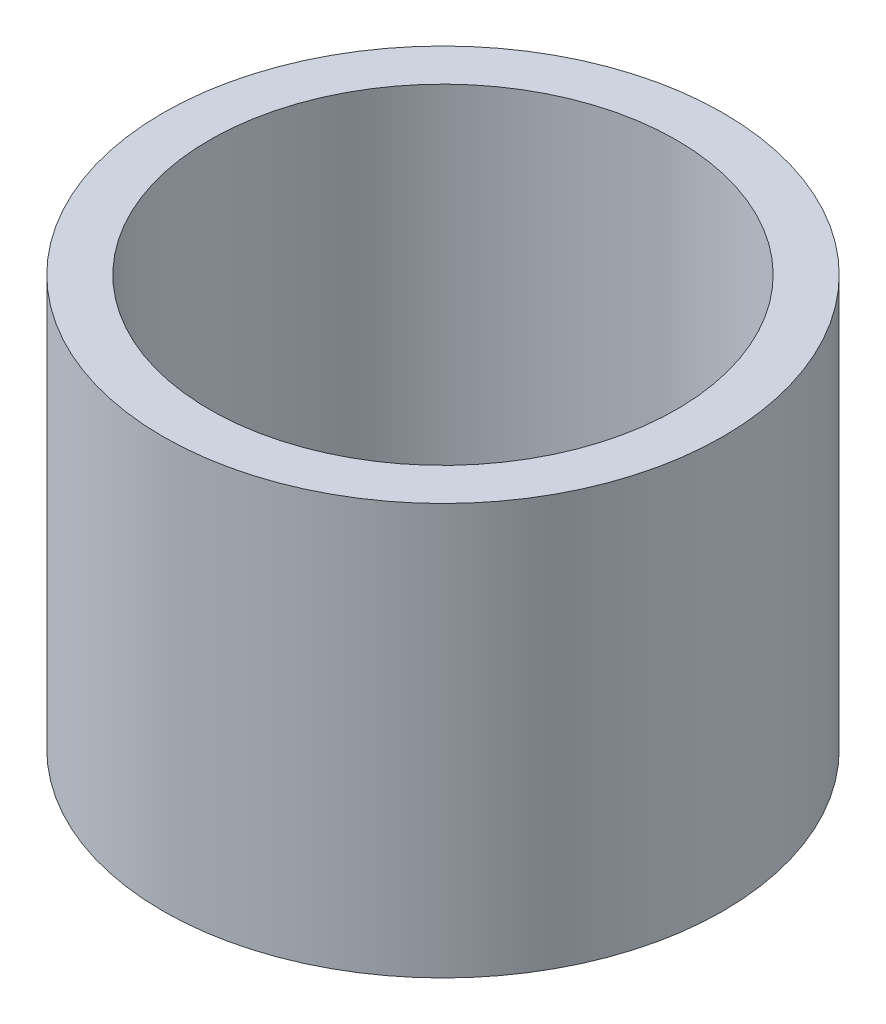
SolidWorks part; units mm, degrees
ref_plane "Front Plane" through (0, 0, 0) normal (0, 0, 1) x (1, 0, 0)
ref_plane "Top Plane" through (0, 0, 0) normal (0, 1, 0) x (1, 0, 0)
ref_plane "Right Plane" through (0, 0, 0) normal (1, 0, 0) x (0, 0, -1)
sketch "Sketch1" plane through (0, 0, 0) normal (0, 1, 0) x (1, 0, 0)
  line L0 (0, 0) -> (0, 11) construction
  line L1 (0, 0) -> (1.1498, 10.9397) construction
  line L2 (0, 0) -> (1.6069, 10.882) construction
  circle A0 centre (0, 0) radius 11 construction
  circle A1 centre (0, 0) radius 9.996 construction
  circle A2 centre (0, 0) radius 10.746 construction
  arc A3 (1.0449, 9.9412) -> (0.5705, 10.3364) centre (1.1029, 10.4932) cw
  arc A4 (2.5291, 10.9132) -> (0.5705, 10.5933) centre (1.5698, 10.6307) cw
  circle A5 centre (0, 0) radius 10.596 construction
  arc A6 (-0.4266, 10.7375) -> (0.4266, 10.7375) centre (0, 0) cw
  arc A7 (0.4266, 10.7375) -> (0.5705, 10.5933) centre (0.4206, 10.5876) cw
  arc A8 (2.5291, 10.9132) -> (0.5705, 10.3364) centre (1.5498, 10.6248) ccw
  arc A9 (-1.0449, 9.9412) -> (-0.5705, 10.3364) centre (-1.1029, 10.4932) ccw
  arc A10 (-2.5291, 10.9132) -> (-0.5705, 10.3364) centre (-1.5498, 10.6248) cw
  arc A11 (-2.5291, 10.9132) -> (-0.5705, 10.5933) centre (-1.5698, 10.6307) ccw
  arc A12 (-0.4266, 10.7375) -> (-0.5705, 10.5933) centre (-0.4206, 10.5876) ccw
  arc A13 (-1.0449, 9.9412) -> (1.0449, 9.9412) centre (0, 0) cw
  point P13 (1.5698, 10.6307)
  point P16 (0, 10.746)
  dimension "D1" = 22
  dimension "D6" = 0.555
  dimension "D7" = 1
  dimension "D9" = 0.15
  dimension "D2" = 6
  dimension "D3" = 2.4
  dimension "D4" = 1.004
  dimension "D5" = 0.75
  dimension "D8" = 0.15
extrude "Boss-Extrude1" add sketch "Sketch1" along normal blind 7 contours A9 A13 A3 A8 A4 A7 A6 A12 A11 A10
sketch "Sketch2" plane through (0, 0, 0) normal (0, -1, 0) x (1, 0, 0)
  circle A0 centre (0, 0) radius 9.996
  arc A2 (-0.8265, -9.9618) -> (0.8265, -9.9618) centre (0, 0) ccw construction
  arc A5 (-0.8265, -9.9618) -> (0.8265, -9.9618) centre (0, 0) ccw
  arc M3 (-0.739, -10.0741) -> (-0.5705, -10.3364) centre (-1.1029, -10.4932) cw
  arc M4 (-0.5705, -10.3364) -> (-0.5309, -10.6893) centre (-1.5498, -10.6248) cw
  arc M5 (-0.8265, -9.9618) -> (-0.739, -10.0741) centre (-1.5698, -10.6307) cw
  arc M6 (-0.5309, -10.6893) -> (-0.4266, -10.7375) centre (-0.4206, -10.5876) ccw
  arc M7 (-0.4266, -10.7375) -> (0.4266, -10.7375) centre (0, 0) ccw
  arc M8 (0.4266, -10.7375) -> (0.5309, -10.6893) centre (0.4206, -10.5876) ccw
  arc M9 (0.739, -10.0741) -> (0.8265, -9.9618) centre (1.5698, -10.6307) cw
  arc M10 (0.5309, -10.6893) -> (0.5705, -10.3364) centre (1.5498, -10.6248) cw
  arc M11 (0.5705, -10.3364) -> (0.739, -10.0741) centre (1.1029, -10.4932) cw
  arc M12 (0.8265, -9.9618) -> (-0.8265, -9.9618) centre (0, 0) cw
extrude "Boss-Extrude2" add sketch "Sketch2" against normal blind 7 contours A0 M3 M12 M11 M10 M9 M8 M7 M6 M5 M4
pattern_circular "CirPattern3" count 30 over 360 about axis through (0, 0, 0) along (0, 1, 0) of "Boss-Extrude1"
sketch "Sketch3" plane through (0, 7, 0) normal (0, 1, 0) x (1, 0, 0)
  circle A0 centre (0, 0) radius 11.946
  arc A3 (0.4742, 11.9366) -> (-0.4742, 11.9366) centre (0, 0) ccw
  arc A4 (0.4742, 11.9366) -> (-0.4742, 11.9366) centre (0, 0) ccw
  dimension "D1" = 1.2
extrude "Boss-Extrude3" add sketch "Sketch3" along normal blind 1.2 contours A0
sketch "Sketch4" plane through (0, 0, 0) normal (0, -1, 0) x (1, 0, 0)
  circle A0 centre (0, 0) radius 11.946 construction
  circle A1 centre (0, 0) radius 11.946
extrude "Boss-Extrude4" add sketch "Sketch4" along normal blind 1.2
sketch "Sketch12" plane through (0, 8.2, 0) normal (0, 1, 0) x (1, 0, 0)
  circle A0 centre (0, 0) radius 7.5
  dimension "D1" = 15
extrude "Boss-Extrude10" add sketch "Sketch12" along normal offset from surface (8.6 mm away) 18 up to face at (0, -1.2, -11.946)
sketch "Sketch5" plane through (0, 8.2, 0) normal (0, 1, 0) x (1, 0, 0)
  circle A0 centre (0, 0) radius 4
  dimension "D1" = 8
extrude "Cut-Extrude1" cut sketch "Sketch5" against normal through all both and the other way through all
chamfer "Chamfer1" distance 0.3 angle 45 3 edges at (0, 7, 11.946) (0, 0, -11.946) (0, 16.8, -7.5)
sketch "Sketch6" plane through (0, 8.2, 0) normal (0, 1, 0) x (1, 0, 0)
  line L0 (0, 0) -> (0, 7.3211) construction
  line L1 (0, 0) -> (0.9969, 7.2529) construction
  line L2 (0, 0) -> (1.3915, 7.1877) construction
  circle A0 centre (0, 0) radius 7.3211 construction
  circle A1 centre (0, 0) radius 6.3171 construction
  circle A2 centre (0, 0) radius 7.0671 construction
  circle A3 centre (0, 0) radius 6.9171 construction
  arc A4 (0.8602, 6.2583) -> (0.6496, 6.3326) centre (0.9358, 6.8081) cw
  arc A5 (0.364, 6.7355) -> (0.3434, 6.9175) centre (1.3432, 6.9383) cw
  arc A6 (-0.1976, 7.0644) -> (0.1976, 7.0644) centre (0, 0) cw
  arc A7 (0.1976, 7.0644) -> (0.3434, 6.9175) centre (0.1935, 6.9144) cw
  arc A8 (0.364, 6.7355) -> (0.6496, 6.3326) centre (0.9672, 6.8604) ccw
  arc A9 (-0.8602, 6.2583) -> (-0.6496, 6.3326) centre (-0.9358, 6.8081) ccw
  arc A10 (-0.364, 6.7355) -> (-0.6496, 6.3326) centre (-0.9672, 6.8604) cw
  arc A11 (-0.364, 6.7355) -> (-0.3434, 6.9175) centre (-1.3432, 6.9383) ccw
  arc A12 (-0.1976, 7.0644) -> (-0.3434, 6.9175) centre (-0.1935, 6.9144) ccw
  arc A13 (-0.8602, 6.2583) -> (0.8602, 6.2583) centre (0, 0) cw
  point P9 (1.3432, 6.9383)
  dimension "D9" = 0.15
  dimension "D4" = 1.004
  dimension "D5" = 0.75
  dimension "D1" = 14.6423
  dimension "D7" = 0.555
  dimension "D8" = 1
  dimension "D3" = 3.13
  dimension "D2" = 7.826
  dimension "D6" = 0.15
extrude "Boss-Extrude5" add sketch "Sketch6" along normal blind 8.2 contours A9 A13 A4 A8 A5 A7 A6 A12 A11 A10
sketch "Sketch7" plane through (0, 8.2, 0) normal (0, 1, 0) x (1, 0, 0)
  circle A0 centre (0, 0) radius 8.2671
  circle A2 centre (0, 0) radius 4 construction
  arc A3 (0.2312, 8.2639) -> (-0.2312, 8.2639) centre (0, 0) ccw
  arc A4 (0.2312, 8.2639) -> (-0.2312, 8.2639) centre (0, 0) ccw
  circle A5 centre (0, 0) radius 4
  dimension "D1" = 1.2
extrude "Boss-Extrude6" add sketch "Sketch7" along normal blind 1.2
sketch "Sketch8" plane through (0, 9.4, 0) normal (0, 1, 0) x (1, 0, 0)
  circle A0 centre (0, 0) radius 6.3171
  arc A1 (0.8602, 6.2583) -> (-0.8602, 6.2583) centre (0, 0) ccw construction
  arc A2 (0.8602, 6.2583) -> (-0.8602, 6.2583) centre (0, 0) ccw
  circle A3 centre (0, 0) radius 4 construction
  circle A4 centre (0, 0) radius 4
extrude "Boss-Extrude7" add sketch "Sketch8" along normal up to surface (7 mm away)
pattern_circular "CirPattern4" count 23 over 360 of "Boss-Extrude5"
sketch "Sketch9" plane through (0, 16.4, 0) normal (0, 1, 0) x (1, 0, 0)
  circle A0 centre (0, 0) radius 8.2671 construction
  circle A1 centre (0, 0) radius 8.2671
  circle A2 centre (0, 0) radius 4 construction
  circle A3 centre (0, 0) radius 4
extrude "Boss-Extrude8" add sketch "Sketch9" along normal blind 1.2
chamfer "Chamfer2" distance 0.3 angle 45 2 edges at (0, 16.4, 8.2671) (0, 9.4, 8.2671)
sketch "Sketch10" plane through (0, -1.2, 0) normal (0, -1, 0) x (1, 0, 0)
  circle A0 centre (0, 0) radius 15
  dimension "D1" = 30
extrude "Boss-Extrude9" add sketch "Sketch10" along normal blind 22
sketch "Sketch11" plane through (0, -23.2, 0) normal (0, -1, 0) x (1, 0, 0)
  circle A0 centre (0, 0) radius 12.5
  dimension "D1" = 25
extrude "Cut-Extrude2" cut sketch "Sketch11" against normal blind 42
equation "\"TeethNumber\"=30"
equation "\"Pitch\"= 2"
equation "\"PulleyDiameter\"= \"TeethNumber\" * \"Pitch\" / PI"
equation "\"ToothAngle\"= ( 360 / \"TeethNumber\" )"
equation "\"TransOffsetAngle\"= \"ToothAngle\" * 0.2' "
equation "\"ShoulderRadius\"= 0.15"
equation "\"RootRadius\"= 0.555"
equation "\"TransRadius\"= 1"
equation "\"ToothHeight\"= 0.75"
equation "\"PLD\"= 0.254"
equation "\"D2@Sketch1\"=\"ToothAngle\"/2"
equation "\"D3@Sketch1\"=\"TransOffsetAngle\""
equation "\"D4@Sketch1\"=\"PLD\"+\"ToothHeight\""
equation "\"D5@Sketch1\"=\"ToothHeight\""
equation "\"D6@Sketch1\" = \"RootRadius\""
equation "\"D7@Sketch1\"=\"TransRadius\""
equation "\"D9@Sketch1\"=\"ShoulderRadius\""
equation "\"TeethNumber-2\"= 23"
equation "\"PulleyDiameter-2\"= \"TeethNumber-2\" * \"Pitch\" / PI"
equation "\"ToothAngle-2\"= 360/\"TeethNumber-2\""
equation "\"TransOffsetAngle-2\"= \"ToothAngle-2\" * 0.2"
equation "\"D1@Sketch6\"=\"PulleyDiameter-2\""
equation "\"D2@Sketch6\"=\"ToothAngle-2\"/2"
equation "\"D3@Sketch6\"=\"TransOffsetAngle-2\""
equation "\"D4@Sketch6\"=\"PLD\"+\"ToothHeight\""
equation "\"D5@Sketch6\"=\"ToothHeight\""
equation "\"D6@Sketch6\"=\"ShoulderRadius\""
equation "\"D7@Sketch6\"=\"RootRadius\""
equation "\"D8@Sketch6\"=\"TransRadius\""
equation "\"D9@Sketch6\"=\"ShoulderRadius\""
equation "\"D1@CirPattern3\"=\"TeethNumber\""
equation "\"D1@CirPattern4\"=\"TeethNumber-2\""
